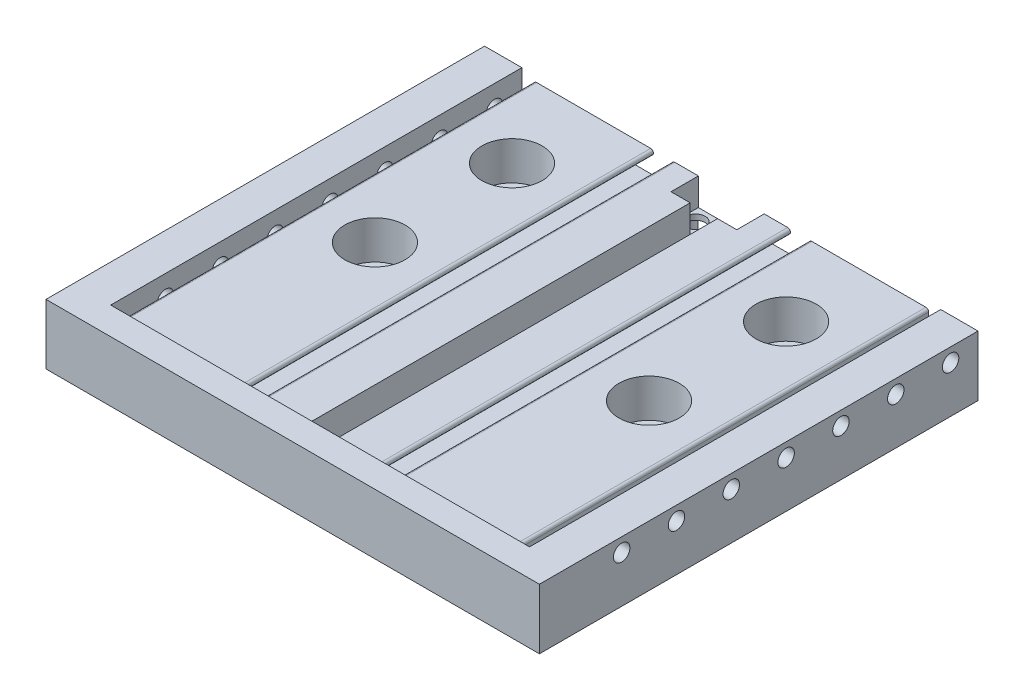
SolidWorks part; units mm, degrees
ref_plane "Front Plane" through (0, 0, 0) normal (0, 0, 1) x (1, 0, 0)
ref_plane "Top Plane" through (0, 0, 0) normal (0, 1, 0) x (1, 0, 0)
ref_plane "Right Plane" through (0, 0, 0) normal (1, 0, 0) x (0, 0, -1)
sketch "Sketch1" plane through (0, 0, 0) normal (0, 1, 0) x (1, 0, 0)
  line L1 (-12.8623, 1.9673) -> (77.1377, 1.9673)
  line L2 (-12.8623, 1.9673) -> (-12.8623, -78.0327)
  line L3 (-12.8623, -78.0327) -> (77.1377, -78.0327)
  line L4 (77.1377, 1.9673) -> (77.1377, -78.0327)
  dimension "D1" = 90
  dimension "D2" = 80
extrude "Boss-Extrude1" add sketch "Sketch1" along normal blind 10
sketch "Sketch2" plane through (0, 10, 0) normal (0, 1, 0) x (1, 0, 0)
  line L0 (77.1377, -78.0327) -> (77.1377, 1.9673) construction
  line L1 (-12.8623, -78.0327) -> (77.1377, -78.0327)
  line L2 (-12.8623, -78.0327) -> (-12.8623, -73.0327)
  line L3 (-5.8623, -73.0327) -> (70.1377, -73.0327)
  line L4 (77.1377, -78.0327) -> (77.1377, -68.0327)
  line L7 (-5.8623, -73.0327) -> (-5.8623, 1.9673)
  line L8 (-5.8623, 1.9673) -> (-12.8623, 1.9673)
  line L9 (-12.8623, -73.0327) -> (-12.8623, 1.9673)
  line L11 (70.1377, -73.0327) -> (70.1377, 1.9673)
  line L12 (70.1377, 1.9673) -> (77.1377, 1.9673)
  line L13 (77.1377, -68.0327) -> (77.1377, 1.9673)
  dimension "D1" = 5
  dimension "D2" = 7
  dimension "D3" = 7
extrude "Boss-Extrude2" add sketch "Sketch2" along normal blind 1
sketch "Sketch3" plane through (0, 10, 0) normal (0, 1, 0) x (1, 0, 0)
  circle A0 centre (57.1377, -38.0327) radius 3.25
  circle A2 centre (7.1377, -38.0327) radius 3.25
  circle A3 centre (32.1377, -38.0327) radius 3.25 [skipped]
  circle A4 centre (7.1377, -13.0327) radius 3.25
  circle A5 centre (57.1377, -13.0327) radius 3.25
  dimension "D1" = 6.5
  dimension "D2" = 3
  dimension "D3" = 2
extrude "Cut-Extrude1" cut sketch "Sketch3" against normal through all
sketch "Sketch4" plane through (0, 10, 0) normal (0, 1, 0) x (1, 0, 0)
  circle A0 centre (7.1377, -38.0327) radius 5.5
  circle A2 centre (57.1377, -38.0327) radius 5.5
  circle A3 centre (32.1377, -38.0327) radius 5.5 [skipped]
  circle A4 centre (57.1377, -13.0327) radius 5.5
  circle A5 centre (7.1377, -13.0327) radius 5.5
  dimension "D1" = 11
  dimension "D2" = 3
  dimension "D3" = 2
extrude "Cut-Extrude2" cut sketch "Sketch4" against normal blind 7
sketch "Sketch5" plane through (0, 0, -1.9673) normal (0, 0, -1) x (-1, 0, 0)
  line L0 (-70.1377, 10) -> (5.8623, 10) construction
  line L1 (-45.6377, 10) -> (-43.6377, 10)
  line L2 (-45.6377, 10) -> (-49.6377, 6)
  line L3 (-49.6377, 6) -> (-39.6377, 6)
  line L4 (-43.6377, 10) -> (-39.6377, 6)
  line L5 (-32.1377, 0) -> (-32.1377, 11) construction
  line L6 (-77.1377, 0) -> (12.8623, 0) construction
  line L7 (-70.1377, 11) -> (5.8623, 11) construction
  line L8 (-14.6377, 6) -> (-24.6377, 6)
  line L9 (-20.6377, 10) -> (-24.6377, 6)
  line L10 (-18.6377, 10) -> (-20.6377, 10)
  line L11 (-18.6377, 10) -> (-14.6377, 6)
  line L12 (-70.1377, 4) -> (-68.1377, 4)
  line L13 (5.8623, 10) -> (3.8623, 10)
  line L14 (5.8623, 10) -> (5.8623, 4)
  line L15 (5.8623, 4) -> (3.8623, 4)
  line L16 (3.8623, 10) -> (3.8623, 4)
  line L17 (-68.1377, 10) -> (-68.1377, 4)
  line L18 (-70.1377, 10) -> (-68.1377, 10)
  line L19 (-70.1377, 10) -> (-70.1377, 4)
  line L20 (-70.1377, 10) -> (5.8623, 10) construction
  line L21 (-34.6377, 10) -> (-29.6377, 10)
  line L22 (-34.6377, 10) -> (-34.6377, 5)
  line L23 (-34.6377, 5) -> (-29.6377, 5)
  line L24 (-29.6377, 10) -> (-29.6377, 5)
  line L25 (-32.1377, 10) -> (-32.1377, -29.7373) construction
  point P16 (-19.6377, 6)
  point P17 (-44.6377, 6)
  point P34 (-32.1377, 5)
  dimension "D1" = 4
  dimension "D2" = 45
  dimension "D3" = 225
  dimension "D4" = 10
  dimension "D5" = 25
  dimension "D6" = 6
  dimension "D7" = 2
  dimension "D8" = 5
  dimension "D9" = 5
extrude "Cut-Extrude3" cut sketch "Sketch5" against normal up to surface (75 mm away) up to face at (32.1377, 10.5, 73.0327)
fillet "Fillet2" radius 0.5 6 edges at (68.1377, 10, 35.5327) (45.6377, 10, 35.5327) (43.6377, 10, 35.5327) (20.6377, 10, 35.5327) (18.6377, 10, 35.5327) (-3.8623, 10, 35.5327)
sketch "Sketch6" plane through (77.1377, 0, 0) normal (1, 0, 0) x (0, 0, -1)
  line L0 (-78.0327, 11) -> (1.9673, 11) construction
  line L1 (1.9673, 11) -> (1.9673, 0) construction
  circle A0 centre (-3.0327, 8.5) radius 1.5
  circle A1 centre (-13.0327, 8.5) radius 1.5
  circle A2 centre (-23.0327, 8.5) radius 1.5
  circle A3 centre (-33.0327, 8.5) radius 1.5
  circle A4 centre (-43.0327, 8.5) radius 1.5
  circle A5 centre (-53.0327, 8.5) radius 1.5
  circle A6 centre (-63.0327, 8.5) radius 1.5
  dimension "D1" = 3
  dimension "D2" = 2.5
  dimension "D3" = 5
  dimension "D4" = 7
extrude "Cut-Extrude4" cut sketch "Sketch6" against normal up to surface (7 mm away) up to face at (70.1377, 7.5, 35.5327)
ref_axis "Axis1" through (32.1377, 10, -1.9673) along (0, -1, 0)
ref_plane "Plane1" through (38.5342, 0, 0) normal (-1, 0, 0) x (0, 0, 1)
sketch "Sketch7" plane through (-12.8623, 0, 0) normal (-1, 0, 0) x (0, 0, 1)
  line L0 (-1.9673, 11) -> (-1.9673, 0) construction
  line L1 (-1.9673, 11) -> (78.0327, 11) construction
  circle A0 centre (3.0327, 7) radius 1.5
  circle A1 centre (13.0327, 7) radius 1.5
  circle A2 centre (23.0327, 7) radius 1.5
  circle A3 centre (33.0327, 7) radius 1.5
  circle A4 centre (43.0327, 7) radius 1.5
  circle A5 centre (53.0327, 7) radius 1.5
  circle A6 centre (63.0327, 7) radius 1.5
  dimension "D1" = 3
  dimension "D2" = 5
  dimension "D3" = 4
  dimension "D4" = 7
extrude "Cut-Extrude5" cut sketch "Sketch7" against normal up to surface (7 mm away) up to face at (-5.8623, 7.5, 35.5327)
sketch "Sketch8" plane through (0, 0, -1.9673) normal (0, 0, -1) x (-1, 0, 0)
  line L0 (-42.4306, 10) -> (-34.6377, 10) construction
  line L1 (-38.1377, 10) -> (-26.1377, 10)
  line L2 (-38.1377, 10) -> (-38.1377, 5)
  line L3 (-38.1377, 5) -> (-26.1377, 5)
  line L4 (-26.1377, 10) -> (-26.1377, 5)
  line L5 (-32.1377, 10) -> (-32.1377, -29.7373) construction
  line L6 (-34.6377, 5) -> (-29.6377, 5) construction
  point P8 (-32.1377, 5)
  point P9 (-37.1377, 3.9297)
  dimension "D1" = 12
extrude "Cut-Extrude6" cut sketch "Sketch8" against normal blind 5
sketch "Sketch9" plane through (0, 5, 0) normal (0, 1, 0) x (1, 0, 0)
  line L0 (32.1377, 1.9673) -> (32.1377, -3.2829) construction
  line L1 (38.1377, 1.9673) -> (26.1377, 1.9673) construction
  line L2 (38.1377, -3.0327) -> (38.1377, 1.9673) construction
  circle A0 centre (36.1377, -0.5327) radius 1.75
  circle A1 centre (28.1377, -0.5327) radius 1.75
  point P10 (36.1377, -0.8429)
  point P11 (38.1377, -0.5327)
  dimension "D1" = 3.5
  dimension "D2" = 2
extrude "Cut-Extrude7" cut sketch "Sketch9" against normal through all
sketch "Sketch10" plane through (0, 0, 0) normal (0, -1, 0) x (1, 0, 0)
  circle A0 centre (36.1377, 0.5327) radius 3
  circle A2 centre (28.1377, 0.5327) radius 3.25
  dimension "D1" = 6
  dimension "D2" = 6.5
extrude "Cut-Extrude8" cut sketch "Sketch10" against normal blind 4
other "Move Face1" flip direction yes face at (70.1377, 8.5, 1.5327) face at (-5.8623, 7, 4.5327) offset 0.2 parameters "D1"=0.2
